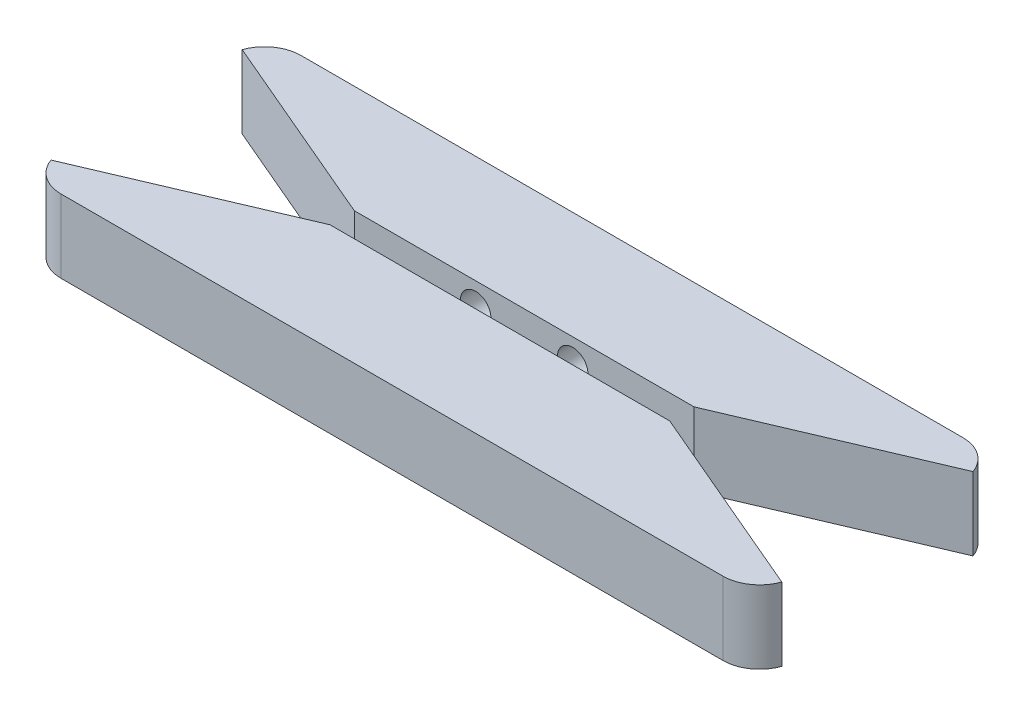
SolidWorks part; units mm, degrees
ref_plane "Front Plane" through (0, 0, 0) normal (0, 0, 1) x (1, 0, 0)
ref_plane "Top Plane" through (0, 0, 0) normal (0, 1, 0) x (1, 0, 0)
ref_plane "Right Plane" through (0, 0, 0) normal (1, 0, 0) x (0, 0, -1)
sketch "Sketch1" plane through (0, 0, 0) normal (0, 1, 0) x (1, 0, 0)
  line L0 (-60, 17.7) -> (60, 17.7)
  line L1 (-27.895, 0) -> (27.895, 0)
  line L2 (-60, 17.7) -> (-60, 13.7)
  line L3 (-60, 13.7) -> (-27.895, 0)
  line L4 (27.895, 0) -> (60, 13.7)
  line L5 (60, 13.7) -> (60, 17.7)
  dimension "D1" = 17.7
  dimension "D2" = 4
  dimension "D3" = 55.79
  dimension "D4" = 120
extrude "Boss-Extrude1" add sketch "Sketch1" along normal blind 12
sketch "Sketch3" plane through (0, 0, 0) normal (0, 0, 1) x (1, 0, 0)
  line L0 (0, -6.6) -> (0, 6.6) construction
  line L1 (-27.895, 12) -> (27.895, 12) construction
  circle A0 centre (-7.97, 8) radius 2.5
  circle A1 centre (7.97, 8) radius 2.5
  dimension "D1" = 5
  dimension "D2" = 4
  dimension "D3" = 15.94
extrude "Cut-Extrude1" cut sketch "Sketch3" against normal blind 8.5
fillet "Fillet1" radius 6 2 edges at (60, 6, -17.7) (-60, 6, -17.7)
ref_plane "Plane1" through (0, 0, 2) normal (0, 0, 1) x (1, 0, 0)
mirror "Mirror2" about plane through (0, 0, 2) normal (0, 0, 1) of bodies 102
